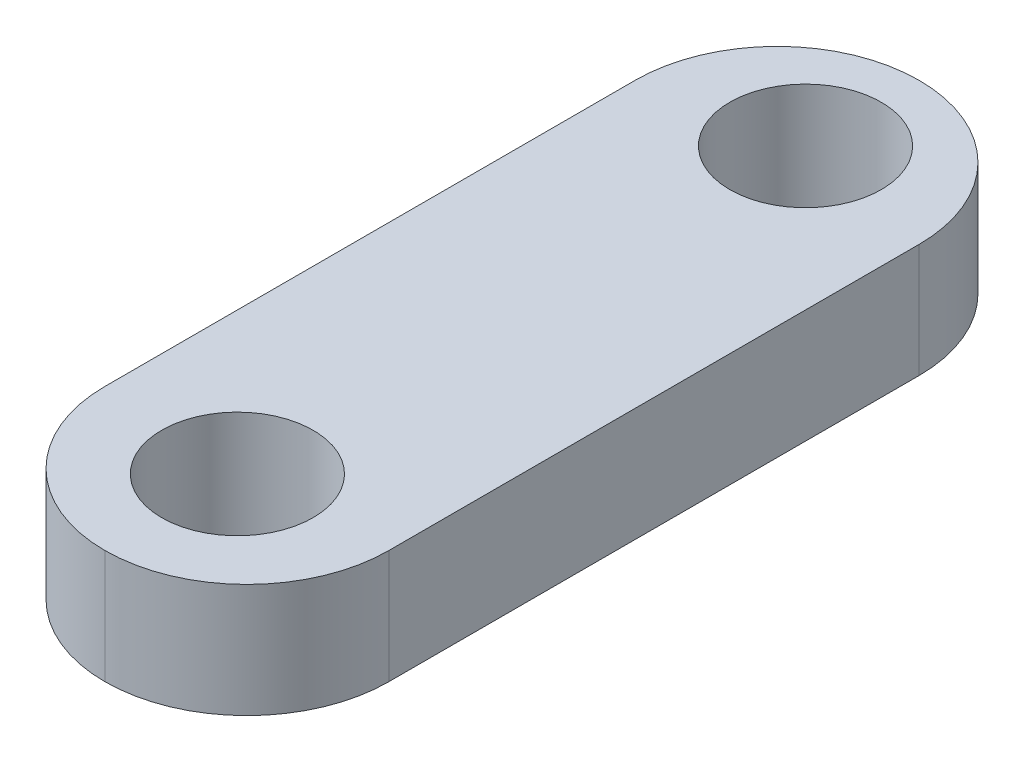
SolidWorks part; units mm, degrees
ref_plane "Front Plane" through (0, 0, 0) normal (0, 0, 1) x (1, 0, 0)
ref_plane "Top Plane" through (0, 0, 0) normal (0, 1, 0) x (1, 0, 0)
ref_plane "Right Plane" through (0, 0, 0) normal (1, 0, 0) x (0, 0, -1)
sketch "Sketch1" plane through (0, 0, 0) normal (0, 1, 0) x (1, 0, 0)
  line L1 (0, 0) -> (15, 0)
  line L2 (0, 0) -> (0, 43)
  line L3 (0, 43) -> (15, 43)
  line L4 (15, 0) -> (15, 43)
  dimension "D1" = 43
  dimension "D2" = 15
extrude "Boss-Extrude1" add sketch "Sketch1" along normal blind 6
sketch "Sketch4" plane through (0, 6, 0) normal (0, 1, 0) x (1, 0, 0)
  line L0 (0, 43) -> (0, 0) construction
  line L1 (0, 0) -> (15, 0) construction
  circle A0 centre (7.5, 37) radius 4
  circle A1 centre (7.5, 7) radius 4
  dimension "D1" = 7.5
  dimension "D2" = 7.5
  dimension "D3" = 30
  dimension "D4" = 7
extrude "Cut-Extrude2" cut sketch "Sketch4" against normal through all
fillet "Fillet1" radius 7.5 4 edges at (0, 3, 0) (15, 3, 0) (15, 3, -43) (0, 3, -43)
